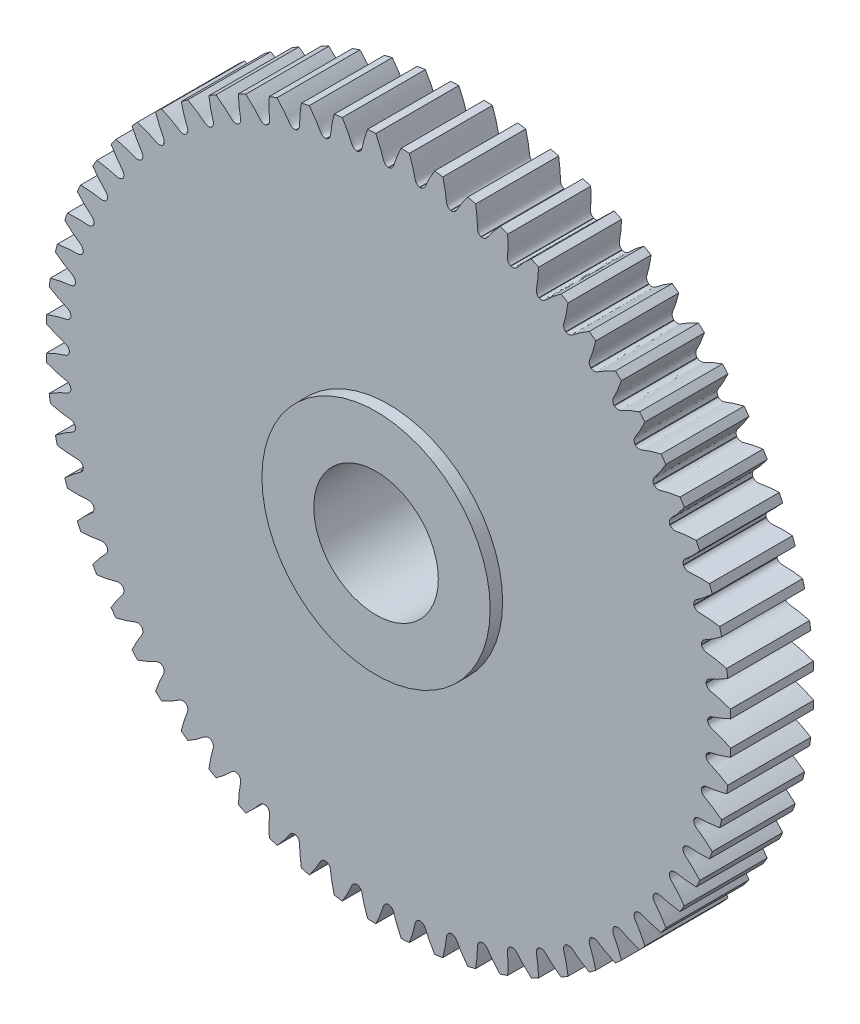
SolidWorks part; units mm, degrees
ref_plane "前视基准面" through (0, 0, 0) normal (0, 0, 1) x (1, 0, 0)
ref_plane "上视基准面" through (0, 0, 0) normal (0, 1, 0) x (1, 0, 0)
ref_plane "右视基准面" through (0, 0, 0) normal (1, 0, 0) x (0, 0, -1)
sketch "草图1" plane through (0, 0, 0) normal (0, 0, 1) x (1, 0, 0)
  circle A0 centre (0, 0) radius 16.5
extrude "凸台-拉伸1" add sketch "草图1" along normal blind 4
ref_axis "基准轴1" through (0, 0, -0.15) along (0, 0, 1)
sketch "草图2" plane through (0, 0, 0) normal (0, 0, 1) x (1, 0, 0)
  line L0 (0, 0) -> (0, 16.5) construction
  circle A0 centre (0, 0) radius 16.5 construction
  arc A1 (0.01, 15.3749) -> (-0.01, 15.3749) centre (0, 0) ccw
  arc A2 (2.2699, 18.763) -> (-2.2699, 18.763) centre (0, 0) ccw
  spline S0 degree 3 poles (0.01, 15.3749) (0.215, 15.4161) (0.2503, 15.5936) (0.3178, 15.7926) (0.3511, 15.8867) (0.3886, 15.9856) (0.4302, 16.0893) (0.4762, 16.1977) (0.5269, 16.3107) (0.5824, 16.4281) (0.6429, 16.5497) (0.7085, 16.6754) (0.7796, 16.805) (0.8563, 16.9385) (0.9387, 17.0755) (1.027, 17.2159) (1.1215, 17.3596) (1.2222, 17.5063) (1.3293, 17.6558) (1.4429, 17.808) (1.5633, 17.9626) (1.6906, 18.1195) (1.8248, 18.2784) (2.0159, 18.4957) (2.1662, 18.6564) (2.2699, 18.763) knots 0 0 0 0 0.106355 0.129132 0.153371 0.179072 0.206233 0.234857 0.264942 0.296488 0.329496 0.363966 0.399897 0.437289 0.476143 0.516459 0.558236 0.601475 0.646175 0.692337 0.73996 0.789045 0.839592 0.891599 1 1 1 1
  spline S1 degree 3 poles (-0.01, 15.3749) (-0.215, 15.4161) (-0.2503, 15.5936) (-0.3178, 15.7926) (-0.3511, 15.8867) (-0.3886, 15.9856) (-0.4302, 16.0893) (-0.4762, 16.1977) (-0.5269, 16.3107) (-0.5824, 16.4281) (-0.6429, 16.5497) (-0.7085, 16.6754) (-0.7796, 16.805) (-0.8563, 16.9385) (-0.9387, 17.0755) (-1.027, 17.2159) (-1.1215, 17.3596) (-1.2222, 17.5063) (-1.3293, 17.6558) (-1.4429, 17.808) (-1.5633, 17.9626) (-1.6906, 18.1195) (-1.8248, 18.2784) (-2.0159, 18.4957) (-2.1662, 18.6564) (-2.2699, 18.763) knots 0 0 0 0 0.106355 0.129132 0.153371 0.179072 0.206233 0.234857 0.264942 0.296488 0.329496 0.363966 0.399897 0.437289 0.476143 0.516459 0.558236 0.601475 0.646175 0.692337 0.73996 0.789045 0.839592 0.891599 1 1 1 1
extrude "切除-拉伸1" cut sketch "草图2" along normal through all
pattern_circular "阵列(圆周)1" count 64 every 5.625 about axis through (0, 0, -0.15) along (0, 0, 1) of "切除-拉伸1"
sketch "草图3" plane through (0, 0, 0) normal (0, 0, 1) x (1, 0, 0)
  circle A0 centre (0, 0) radius 16 construction
  dimension "Dn" = 32
sketch "草图6" plane through (0, 0, 0) normal (0, 0, -1) x (-1, 0, 0)
  circle A0 centre (0, 0) radius 5.5
  dimension "D1" = 11
extrude "凸台-拉伸3" add sketch "草图6" against normal blind 10.6 from offset 6
sketch "草图7" plane through (0, 0, 4.6) normal (0, 0, 1) x (1, 0, 0)
  circle A0 centre (0, 0) radius 3
  dimension "D1" = 6
extrude "切除-拉伸2" cut sketch "草图7" against normal through all
sketch "草图9" plane through (0, 0, 0) normal (1, 0, 0) x (0, 0, -1)
  line L0 (0, 0) -> (6, 0) construction
  line L1 (6, -5.5) -> (6, 5.5) construction
hole_wizard "M4 螺纹孔1" positions "草图10" profile "草图11" tap size "M4" standard "GB"
sketch "草图10" plane through (0, 0, 0) normal (1, 0, 0) x (0, 0, -1)
  line L0 (0, 0) -> (6, 0) construction
  point P0 (3, 0)
sketch "草图11" plane through (0, 0, -3) normal (0, 1, 0) x (0, 0, -1)
  line L0 (0, 0) -> (0, 12.4914)
  line L1 (0, 12.4914) -> (1.65, 11.5)
  line L2 (1.65, 11.5) -> (1.65, 0)
  line L5 (1.65, 0) -> (0, 0)
  line L10 (0, 12.4914) -> (-1.65, 11.5) construction
  line L11 (0, -6.35) -> (0, 107.95) construction
  dimension "螺纹孔钻头直径" = 3.3
  dimension "螺纹孔钻头深度" = 11.5
  dimension "导头角度" = 118
cosmetic thread "孔螺蚊线1" parameters "D1"=5.5, "D2"=4
